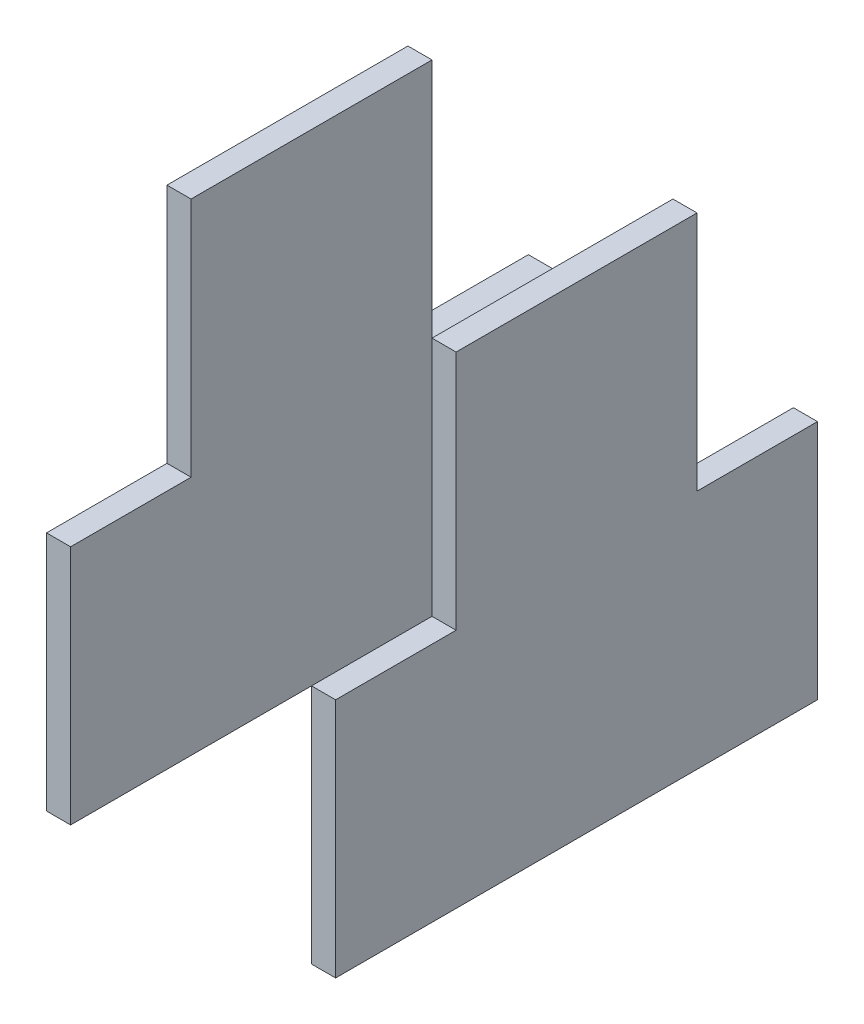
SolidWorks part; units mm, degrees
ref_plane "Front Plane" through (0, 0, 0) normal (0, 0, 1) x (1, 0, 0)
ref_plane "Top Plane" through (0, 0, 0) normal (0, 1, 0) x (1, 0, 0)
ref_plane "Right Plane" through (0, 0, 0) normal (1, 0, 0) x (0, 0, -1)
sketch "Sketch1" plane through (0, 0, 0) normal (0, 1, 0) x (1, 0, 0)
  line L1 (0, 0) -> (12.7, 0)
  line L2 (0, 0) -> (0, 152.4)
  line L3 (0, 152.4) -> (12.7, 152.4)
  line L4 (12.7, 0) -> (12.7, 152.4)
  dimension "D1" = 12.7
  dimension "D2" = 152.4
extrude "Boss-Extrude1" add sketch "Sketch1" along normal blind 25.4
sketch "Sketch6" plane through (12.7, 0, 0) normal (1, 0, 0) x (0, 0, -1)
  line L0 (0, 25.4) -> (152.4, 25.4) construction
  line L1 (152.4, 0) -> (101.6, 0)
  line L2 (152.4, 0) -> (152.4, 25.4)
  line L3 (152.4, 25.4) -> (101.6, 25.4)
  line L4 (101.6, 0) -> (101.6, 25.4)
  dimension "D1" = 50.8
extrude "Boss-Extrude5" add sketch "Sketch6" along normal blind 2.54 contours L2 L1 L4 L3
sketch "Sketch7" plane through (0, 25.4, 0) normal (0, 1, 0) x (1, 0, 0)
  line L0 (12.7, 101.6) -> (12.7, 152.4) construction
  line L1 (15.24, 152.4) -> (0, 152.4) construction
  line L3 (15.24, 152.4) -> (15.24, 101.6) construction
  line L4 (12.7, 114.3) -> (15.24, 114.3)
  line L5 (12.7, 114.3) -> (12.7, 139.7)
  line L6 (12.7, 139.7) -> (15.24, 139.7)
  line L7 (15.24, 114.3) -> (15.24, 139.7)
  point P8 (12.7, 127)
extrude "Boss-Extrude6" add sketch "Sketch7" along normal blind 25.4
mirror "Mirror1" about plane through (0, 25.4, 0) normal (1, 0, 0) of "Boss-Extrude6", "Boss-Extrude1", "Boss-Extrude5"
sketch "Sketch8" plane through (0, 0, 0) normal (0, 0, 1) x (1, 0, 0)
  line L1 (-12.7, 0) -> (12.7, 0)
  line L2 (-12.7, 0) -> (-12.7, 25.4)
  line L3 (-12.7, 25.4) -> (12.7, 25.4)
  line L4 (12.7, 0) -> (12.7, 25.4)
extrude "Cut-Extrude1" cut sketch "Sketch8" against normal blind 170.18
